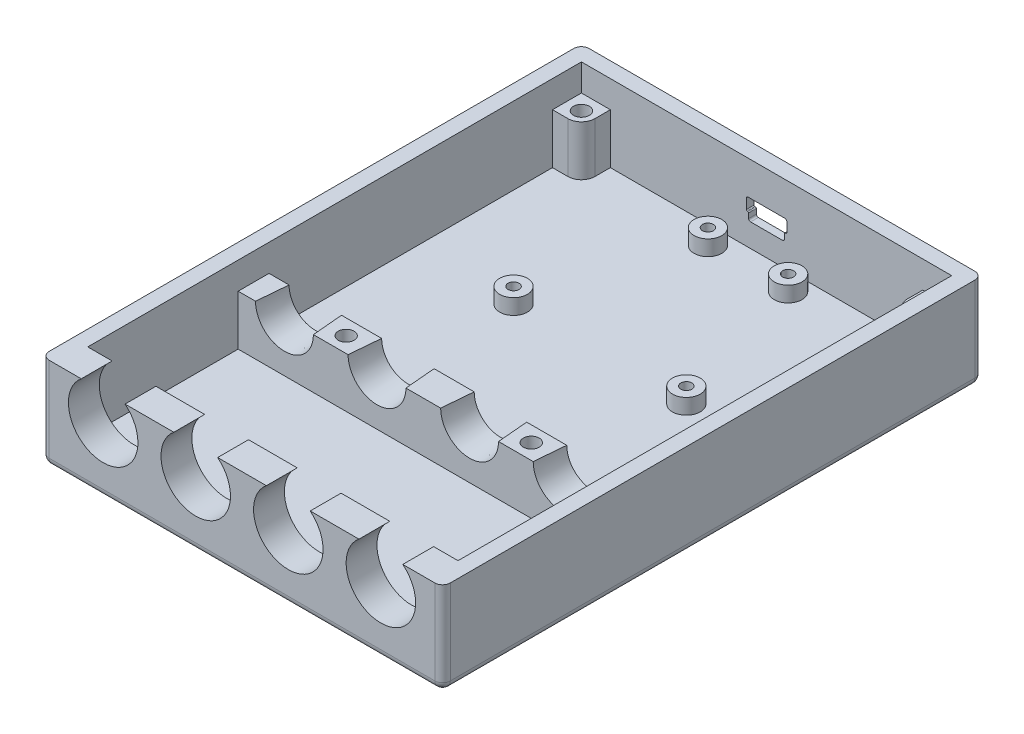
SolidWorks part; units mm, degrees
ref_plane "Front Plane" through (0, 0, 0) normal (0, 0, 1) x (1, 0, 0)
ref_plane "Top Plane" through (0, 0, 0) normal (0, 1, 0) x (1, 0, 0)
ref_plane "Right Plane" through (0, 0, 0) normal (1, 0, 0) x (0, 0, -1)
sketch "Sketch1" plane through (0, 0, 0) normal (0, 1, 0) x (1, 0, 0)
  line L1 (-41.275, -55.5625) -> (41.275, -55.5625)
  line L2 (-41.275, -55.5625) -> (-41.275, 55.5625)
  line L3 (-41.275, 55.5625) -> (41.275, 55.5625)
  line L4 (41.275, -55.5625) -> (41.275, 55.5625)
  line L5 (-41.275, -55.5625) -> (41.275, 55.5625) construction
  line L6 (-41.275, 55.5625) -> (41.275, -55.5625) construction
  point P0 (0, 0)
  dimension "D1" = 82.55
  dimension "D2" = 111.125
extrude "Boss-Extrude1" add sketch "Sketch1" along normal blind 19.05
sketch "Sketch11" plane through (0, 0, 55.5625) normal (0, 0, 1) x (1, 0, 0)
  line L0 (0, 19.05) -> (0, 6.35) construction
  line L1 (-41.275, 19.05) -> (41.275, 19.05) construction
  line L2 (-41.275, 6.35) -> (41.275, 6.35) construction
  line L3 (-41.275, 19.05) -> (-41.275, 0) construction
  line L4 (41.275, 19.05) -> (41.275, 0) construction
  circle A0 centre (-28.575, 13.5001) radius 7.1501
  circle A1 centre (-9.525, 13.5001) radius 7.1501
  circle A2 centre (9.525, 13.5001) radius 7.1501
  circle A3 centre (28.575, 13.5001) radius 7.1501
  point P11 (-38.1, 6.35)
  point P12 (-28.575, 6.35)
  point P13 (-9.525, 6.35)
  point P14 (9.525, 6.35)
  point P15 (28.575, 6.35)
  point P16 (38.1, 6.35)
  point P17 (-28.575, 20.6502)
  point P18 (-9.525, 20.6502)
  point P19 (9.525, 20.6502)
  point P20 (28.575, 20.6502)
  dimension "D1" = 12.7
  dimension "D2" = 3.175
  dimension "D3" = 9.525
  dimension "D4" = 19.05
  dimension "D5" = 19.05
  dimension "D6" = 19.05
  dimension "D7" = 3.175
  dimension "D8" = 9.525
  dimension "D9" = 14.3002
  dimension "D10" = 14.3002
  dimension "D11" = 14.3002
  dimension "D12" = 14.3002
sketch "Sketch14" plane through (0, 19.05, 0) normal (0, 1, 0) x (-1, 0, 0)
  line L0 (0, 0) -> (0, -1.5875) construction
  line L3 (38.1, 49.2125) -> (-38.1, 49.2125)
  line L4 (38.1, 49.2125) -> (38.1, -52.3875)
  line L5 (38.1, -52.3875) -> (-38.1, -52.3875)
  line L6 (-38.1, 49.2125) -> (-38.1, -52.3875)
  line L7 (38.1, 49.2125) -> (-38.1, -52.3875) construction
  line L8 (38.1, -52.3875) -> (-38.1, 49.2125) construction
  dimension "D1" = 1.5875
  dimension "D2" = 101.6
  dimension "D3" = 76.2
extrude "Cut-Extrude3" cut sketch "Sketch14" against normal offset from surface (15.875 mm away) 3.175 up to face at (0, 0, 0)
extrude "Cut-Extrude4" cut sketch "Sketch11" against normal up to next
sketch "Sketch16" plane through (0, 0, 49.2125) normal (0, 0, -1) x (-1, 0, 0)
  point P0 (28.575, 13.5001)
  point P1 (-28.575, 13.5001)
sketch3d "ControllerCenter"
sketch "Sketch17" plane through (0, 3.175, 0) normal (0, 1, 0) x (-1, 0, 0)
  line L0 (0, 49.2125) -> (0, 18.2562) construction
  line L1 (5.0169, 49.2125) -> (-5.0169, 49.2125) construction
  line L2 (38.1, 18.2562) -> (-38.1, 18.2562)
  line L3 (38.1, 18.2562) -> (38.1, 11.9062)
  line L4 (-38.1, 18.2562) -> (-38.1, 11.9062)
  line L5 (38.1, 11.9062) -> (-38.1, 11.9062)
  line L6 (38.1, -52.3875) -> (38.1, 49.2125) construction
  line L7 (-38.1, 49.2125) -> (-38.1, -52.3875) construction
  line L8 (0, -52.3875) -> (0, 11.9062) construction
  line L9 (-38.1, -52.3875) -> (38.1, -52.3875) construction
  line L10 (32.1469, -49.2125) -> (32.1469, -52.3875)
  line L11 (-38.1, -52.3875) -> (38.1, -52.3875) construction
  line L12 (34.925, -46.4344) -> (38.1, -46.4344)
  line L13 (38.1, -52.3875) -> (32.1469, -52.3875)
  line L14 (-32.1469, -49.2125) -> (-32.1469, -52.3875)
  line L15 (-34.925, -46.4344) -> (-38.1, -46.4344)
  line L16 (-38.1, -46.4344) -> (-38.1, -52.3875)
  line L17 (-38.1, -52.3875) -> (-32.1469, -52.3875)
  line L18 (38.1, -46.4344) -> (38.1, -52.3875)
  arc A0 (34.925, -46.4344) -> (32.1469, -49.2125) centre (34.925, -49.2125) ccw
  arc A1 (-34.925, -46.4344) -> (-32.1469, -49.2125) centre (-34.925, -49.2125) cw
  dimension "D5" = 5.5562
  dimension "D1" = 30.9562
  dimension "D2" = 6.35
  dimension "D3" = 3.175
  dimension "D4" = 3.175
extrude "Boss-Extrude4" add sketch "Sketch17" along normal up to surface (10.3251 mm away)
sketch "Sketch18" plane through (0, 0, 18.2562) normal (0, 0, 1) x (1, 0, 0)
  line L0 (-38.1, 13.5001) -> (38.1, 13.5001) construction
  circle A0 centre (-28.575, 13.5001) radius 5.9531
  circle A1 centre (-9.525, 13.5001) radius 5.9531
  circle A2 centre (9.525, 13.5001) radius 5.9531
  circle A3 centre (28.575, 13.5001) radius 5.9531
  point P0 (-28.575, 13.5001)
  point P1 (-9.525, 13.5001)
  point P4 (9.525, 13.5001)
  point P5 (28.575, 13.5001)
  dimension "D6" = 11.9062
  dimension "D7" = 11.9062
  dimension "D8" = 11.9062
  dimension "D9" = 11.9062
  dimension "D1" = 9.525
  dimension "D2" = 19.05
  dimension "D3" = 19.05
  dimension "D4" = 19.05
  dimension "D5" = 9.525
extrude "Cut-Extrude5" cut sketch "Sketch18" against normal up to next (6.35 mm away) draft 5
sketch "Sketch19" plane through (0, 3.175, 0) normal (0, 1, 0) x (-1, 0, 0)
  line L0 (38.1, -17.2641) -> (-38.1, -17.2641) construction
  line L1 (38.1, -46.4344) -> (38.1, 11.9062) construction
  line L2 (-38.1, 11.9062) -> (-38.1, -46.4344) construction
  line L3 (8.255, -52.3875) -> (8.255, 11.9062) construction
  line L4 (-38.1, -52.3875) -> (38.1, -52.3875) construction
  line L5 (-38.1, 11.9062) -> (38.1, 11.9062) construction
  line L6 (-8.255, -52.3875) -> (-8.255, 11.9062) construction
  line L7 (-32.1469, -52.3875) -> (32.1469, -52.3875) construction
  circle A0 centre (8.255, -48.5775) radius 2.8575
  circle A1 centre (-8.255, -48.5775) radius 2.8575
  circle A2 centre (17.78, -18.0975) radius 2.8575
  circle A3 centre (-17.78, -18.0975) radius 2.8575
  point P6 (8.255, -17.2641)
  point P7 (-8.255, -17.2641)
  point P18 (8.255, -48.5775)
  point P19 (-8.255, -48.5775)
  point P20 (8.255, -18.0975)
  point P21 (-8.255, -18.0975)
  dimension "D7" = 5.715
  dimension "D8" = 5.715
  dimension "D9" = 9.525
  dimension "D10" = 9.525
  dimension "D11" = 5.715
  dimension "D12" = 5.715
  dimension "D1" = 16.51
  dimension "D2" = 29.845
  dimension "D3" = 3.81
  dimension "D4" = 3.81
  dimension "D5" = 30.48
  dimension "D6" = 30.48
sketch "Sketch21" plane through (0, 0, -55.5625) normal (0, 0, -1) x (-1, 0, 0)
  line L0 (0, 19.05) -> (0, 0) construction
  line L1 (-41.275, 19.05) -> (41.275, 19.05) construction
  line L2 (0, 7.9375) -> (3.683, 7.9375) construction
  line L3 (-3.683, 7.9375) -> (-3.683, 9.525)
  line L4 (-3.683, 7.9375) -> (3.683, 7.9375)
  line L5 (-3.683, 9.525) -> (-4.1672, 9.525)
  line L6 (4.1672, 9.525) -> (4.1672, 12.1047)
  line L7 (-4.1672, 12.1047) -> (4.1672, 12.1047)
  line L8 (-4.1672, 9.525) -> (-4.1672, 12.1047)
  line L9 (-4.1672, 12.1047) -> (4.1672, 7.9375) construction
  line L10 (-4.1672, 7.9375) -> (4.1672, 12.1047) construction
  line L14 (3.683, 7.9375) -> (3.683, 9.525)
  line L15 (3.683, 9.525) -> (4.1672, 9.525)
  point P11 (0, 12.1047)
  point P13 (0, 10.0211)
  dimension "D1" = 4.1672
  dimension "D2" = 3.683
  dimension "D3" = 1.5875
  dimension "D4" = 2.5797
extrude "Cut-Extrude7" cut sketch "Sketch21" against normal up to next
fillet "Fillet6" radius 1.5875 8 edges at (-41.275, 0, 0) (-41.275, 9.525, -55.5625) (0, 0, -55.5625) (41.275, 9.525, -55.5625) (41.275, 0, 0) (0, 0, 55.5625) (41.275, 9.525, 55.5625) (-41.275, 9.525, 55.5625)
sketch "Sketch25" plane through (0, 0, -52.3875) normal (0, 0, 1) x (1, 0, 0)
  line L0 (-5.2218, 3.175) -> (-5.2218, 19.05) construction
  line L1 (32.1469, 3.175) -> (-32.1469, 3.175) construction
  line L2 (38.1, 19.05) -> (-38.1, 19.05) construction
  point P4 (-5.2218, 6.35)
  point P7 (-5.2218, 7.9375)
  dimension "D1" = 3.175
  dimension "D2" = 1.5875
sketch3d "BoardTop"
extrude "Boss-Extrude8" add sketch "Sketch19" along normal offset from surface (3.175 mm away) 1.5875
sketch "HoleLocations" plane through (0, 13.5001, 0) normal (0, 1, 0) x (-1, 0, 0)
  point P0 (19.05, 15.0812)
  point P1 (-19.05, 15.0812)
  point P2 (34.925, -49.2125)
  point P3 (-34.925, -49.2125)
sketch "HoleLocationsUnder" plane through (0, 0, 0) normal (0, -1, 0) x (1, 0, 0)
  point P0 (-19.05, 15.0812)
  point P1 (19.05, 15.0812)
hole_wizard "CBORE for #4 Pan Head Machine Screw3" positions "Sketch34" profile "Sketch35" counterbore size "#4" standard "Ansi Inch" end condition through all
sketch "Sketch34" plane through (0, 0, 0) normal (0, -1, 0) x (1, 0, 0)
  point P0 (-19.05, 15.0812)
  point P4 (19.05, 15.0812)
  point P7 (-34.925, -49.2125)
  point P10 (34.925, -49.2125)
sketch "Sketch35" plane through (-19.05, 0, 15.0812) normal (1, 0, 0) x (0, 0, -1)
  line L0 (0, 0) -> (0, 19.05)
  line L1 (0, 19.05) -> (1.6319, 19.05)
  line L3 (1.6319, 19.05) -> (1.632, 2.032)
  line L4 (1.632, 2.032) -> (3.175, 2.032)
  line L5 (3.175, 2.032) -> (3.175, 0)
  line L7 (3.175, 0) -> (0, 0)
  line L11 (0, -6.35) -> (0, 107.95) construction
  dimension "Thru Hole Dia." = 3.2639
  dimension "Thru Hole Depth" = 19.05
  dimension "C'Bore Dia." = 6.35
  dimension "C'Bore Depth" = 2.032
hole_wizard "#4-40 Tapped Hole1" positions "Sketch37" profile "Sketch38" tap size "#4-40" standard "Ansi Inch"
sketch "Sketch37" plane through (-31.8238, 6.35, 11.9974) normal (0, 1, 0) x (-1, 0, 0)
  point P0 (-23.5688, -60.5749)
  point P4 (-14.0438, -30.0949)
  point P7 (-49.6038, -30.0949)
  point P10 (-40.0788, -60.5749)
sketch "Sketch38" plane through (-8.255, 6.35, -48.5775) normal (1, 0, 0) x (0, 0, 1)
  line L0 (0, 0) -> (0, 5.4544)
  line L1 (0, 5.4544) -> (1.1303, 4.7752)
  line L2 (1.1303, 4.7752) -> (1.1303, 0)
  line L5 (1.1303, 0) -> (0, 0)
  line L10 (0, 5.4544) -> (-1.1303, 4.7752) construction
  line L11 (0, -6.35) -> (0, 107.95) construction
  dimension "Tap Drill Dia." = 2.2606
  dimension "Tap Drill Depth" = 4.7752
  dimension "Drill Angle" = 118
cosmetic thread "Hole Thread1" parameters "D1"=4.7752, "D2"=2.8448
cosmetic thread "Hole Thread2" parameters "D1"=4.7752, "D2"=2.8448
cosmetic thread "Hole Thread3" parameters "D1"=4.7752, "D2"=2.8448
cosmetic thread "Hole Thread4" parameters "D1"=4.7752, "D2"=2.8448
sketch "Sketch39" plane through (0, 0, -55.5625) normal (0, 0, -1) x (-1, 0, 0)
  line L0 (-4.1672, 12.1047) -> (4.1672, 7.9375) construction
  line L1 (4.1672, 12.1047) -> (-4.1672, 7.9375) construction
  line L3 (-8.7312, 2.8773) -> (8.7313, 2.8773)
  line L4 (-8.7312, 2.8773) -> (-8.7312, 17.1648)
  line L5 (-8.7312, 17.1648) -> (8.7313, 17.1648)
  line L6 (8.7313, 2.8773) -> (8.7313, 17.1648)
  line L7 (-8.7312, 2.8773) -> (8.7313, 17.1648) construction
  line L8 (-8.7312, 17.1648) -> (8.7313, 2.8773) construction
  point P6 (0, 10.0211)
  dimension "D1" = 14.2875
  dimension "D2" = 17.4625
extrude "Cut-Extrude8" cut sketch "Sketch39" against normal blind 1.5875
fillet "Fillet7" radius 0.7937 4 edges at (8.7312, 2.8773, -54.7688) (-8.7313, 2.8773, -54.7688) (-8.7313, 17.1648, -54.7688) (8.7312, 17.1648, -54.7688)
fillet "Fillet8" radius 0.1984 4 edges at (-4.1672, 9.525, -53.1813) (-3.683, 9.525, -53.1813) (4.1672, 9.525, -53.1813) (3.683, 9.525, -53.1813)
fillet "Fillet9" radius 0.3969 4 edges at (3.683, 7.9375, -53.1813) (-3.683, 7.9375, -53.1813) (-4.1672, 12.1047, -53.1813) (4.1672, 12.1047, -53.1813)
